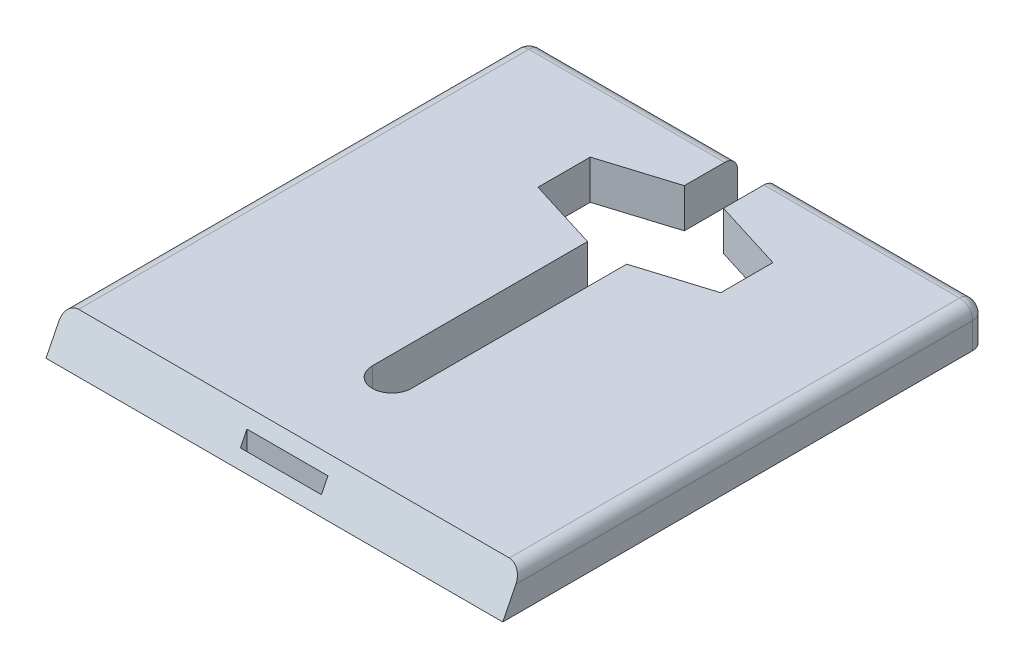
SolidWorks part; units mm, degrees
ref_plane "Ebene vorne" through (0, 0, 0) normal (0, 0, 1) x (1, 0, 0)
ref_plane "Ebene oben" through (0, 0, 0) normal (0, 1, 0) x (1, 0, 0)
ref_plane "Ebene rechts" through (0, 0, 0) normal (1, 0, 0) x (0, 0, -1)
sketch "Skizze1" plane through (0, 0, 0) normal (0, 1, 0) x (1, 0, 0)
  line L1 (-8.75, -9.25) -> (8.75, -9.25)
  line L2 (-8.75, -9.25) -> (-8.75, 9.25)
  line L3 (-8.75, 9.25) -> (8.75, 9.25)
  line L4 (8.75, -9.25) -> (8.75, 9.25)
  line L5 (-8.75, -9.25) -> (8.75, 9.25) construction
  line L6 (-8.75, 9.25) -> (8.75, -9.25) construction
  point P0 (0, 0)
  dimension "D1" = 18.5
  dimension "D2" = 17.5
extrude "Aufsatz-Linear austragen1" add sketch "Skizze1" along normal blind 1.5
fillet "Verrundung1" radius 0.5 3 edges at (8.75, 1.5, 0) (0, 1.5, -9.25) (-8.75, 1.5, 0)
sketch "Skizze2" plane through (-8.75, 0, 0) normal (-1, 0, 0) x (0, 0, 1)
  line L0 (9.25, 0) -> (8.5, 1.5)
  line L1 (-8.75, 1.5) -> (9.25, 1.5) construction
  line L2 (8.5, 1.5) -> (9.25, 1.5)
  line L3 (9.25, 1.5) -> (9.25, 0)
  dimension "D1" = 0.75
extrude "Schnitt-Linear austragen1" cut sketch "Skizze2" against normal up to surface (17.5 mm away) up to face at (8.75, 0.5, 0)
fillet "Verrundung2" radius 0.5 4 edges at (8.6036, 1.3536, -9.1036) (-8.6036, 1.3536, -9.1036) (8.75, 0.5, -9.25) (-8.75, 0.5, -9.25)
sketch "Skizze5" plane through (0, 1.5, 0) normal (0, 1, 0) x (1, 0, 0)
  line L0 (-8.75, 8.75) -> (-8.75, -9.25) construction
  line L1 (-3.5, 4.35) -> (3.5, 4.35)
  line L2 (-3.5, 4.35) -> (-3.5, 6.35)
  line L3 (-3.5, 6.35) -> (3.5, 6.35)
  line L4 (3.5, 4.35) -> (3.5, 6.35)
  line L5 (-3.5, 4.35) -> (3.5, 6.35) construction
  line L6 (-3.5, 6.35) -> (3.5, 4.35) construction
  line L7 (-8.25, 9.25) -> (8.25, 9.25) construction
  circle A0 centre (0, 5.35) radius 2
  dimension "D2" = 4
  dimension "D1" = 7
  dimension "D3" = 2
  dimension "D4" = 8.75
  dimension "D5" = 3.9
extrude "Schlüsselloch" cut sketch "Skizze5" against normal up to surface (1.5 mm away) contours A0 L3 L2 L1 | L3 A0 | L1 A0 L3 | L1 A0 | A0 L1 L4 L3 region at (-2.7046, 1.5, -5.35) region at (0, 1.5, -5.35) region at (0, 1.5, -3.94) region at (2.7046, 1.5, -5.35) region at (0, 1.5, -6.76) up to face at (0, 0, -2.9512)
sketch "Skizze6" plane through (0, 1.5, 0) normal (0, 1, 0) x (1, 0, 0)
  line L0 (8.25, -8.5) -> (-8.25, -8.5) construction
  line L1 (-1.5515, -9) -> (1.5515, -9)
  line L2 (-1.5515, -9) -> (-1.5515, -8.75)
  line L3 (-1.5515, -8.75) -> (1.5515, -8.75)
  line L4 (1.5515, -9) -> (1.5515, -8.75)
  line L5 (-1.5515, -9) -> (1.5515, -8.75) construction
  line L6 (-1.5515, -8.75) -> (1.5515, -9) construction
  line L7 (-8.75, -8.75) -> (-8.75, -9.25) construction
  point P0 (0, -8.875)
  dimension "D1" = 0.25
  dimension "D2" = 0.25
  dimension "D3" = 8.75
extrude "Griff" cut sketch "Skizze6" against normal up to surface (1.5 mm away) up to face at (0, 0, -5.35)
sketch "Skizze7" plane through (0, 1.5, 0) normal (0, 1, 0) x (1, 0, 0)
  line L5 (0, 9.25) -> (0, -4.75) construction
  line L6 (-8.25, 9.25) -> (8.25, 9.25) construction
  line L7 (0.75, 9.25) -> (0.75, -4.75)
  line L8 (-0.75, 9.25) -> (-0.75, -4.75)
  arc A0 (0.75, 9.25) -> (-0.75, 9.25) centre (0, 9.25) ccw
  arc A1 (-0.75, -4.75) -> (0.75, -4.75) centre (0, -4.75) ccw
  point P4 (0, 2.25)
  dimension "D1" = 14
  dimension "D2" = 1.5
extrude "Langloch_Antenne" cut sketch "Skizze7" against normal up to surface (1.5 mm away) up to face at (0, 0, 8.875)
sketch "Skizze8" plane through (0, 1.5, 0) normal (0, 1, 0) x (1, 0, 0)
  line L0 (3.5, 4.35) -> (0.75, 3.496)
  line L1 (0.75, 3.496) -> (-0.75, 3.496)
  line L2 (-0.75, 3.496) -> (-3.5, 4.35)
  line L3 (-3.5, 4.35) -> (-3.5, 6.35)
  line L4 (-3.5, 6.35) -> (-0.75, 7.204)
  line L5 (-0.75, 7.204) -> (0.75, 7.204)
  line L6 (0.75, 7.204) -> (3.5, 6.35)
  line L7 (3.5, 6.35) -> (3.5, 4.35)
extrude "Schnitt-Linear austragen2" cut sketch "Skizze8" against normal up to surface (1.5 mm away) up to face at (0, 0, -4.0981)
